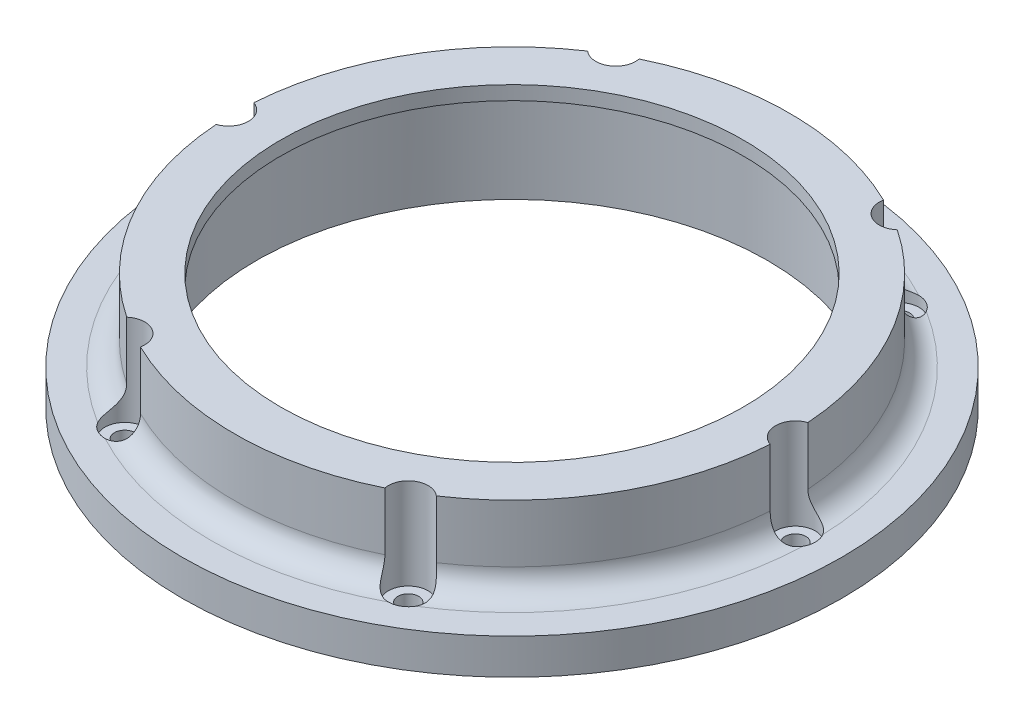
SolidWorks part; units mm, degrees
ref_plane "Front Plane" through (0, 0, 0) normal (0, 0, 1) x (1, 0, 0)
ref_plane "Top Plane" through (0, 0, 0) normal (0, 1, 0) x (1, 0, 0)
ref_plane "Right Plane" through (0, 0, 0) normal (1, 0, 0) x (0, 0, -1)
sketch "Sketch1" plane through (0, 0, 0) normal (0, 1, 0) x (1, 0, 0)
  circle A0 centre (0, 0) radius 61.25 construction
  circle A1 centre (0, 0) radius 55.25
  circle A2 centre (0, 0) radius 60
  dimension "D1" = 122.5
  dimension "D2" = 110.5
  dimension "D3" = 120
extrude "Boss-Extrude1" add sketch "Sketch1" along normal blind 22
sketch "Sketch2" plane through (0, 0, 0) normal (0, -1, 0) x (1, 0, 0)
  circle A0 centre (0, 0) radius 61.25 construction
  circle A1 centre (0, 0) radius 71.25
  circle A2 centre (0, 0) radius 60 construction
  circle A3 centre (0, 0) radius 60
  dimension "D1" = 122.5
  dimension "D2" = 10
extrude "Boss-Extrude2" add sketch "Sketch2" against normal blind 7.5
sketch "Sketch11" plane through (0, 22, 0) normal (0, 1, 0) x (1, 0, 0)
  circle A2 centre (0, 0) radius 60
  circle A3 centre (0, 0) radius 50
  dimension "D1" = 120
  dimension "D2" = 100
extrude "Boss-Extrude5" add sketch "Sketch11" along normal blind 3
hole_wizard "CBORE for M4 SBHCS1" positions "Sketch6" profile "Sketch5" counterbore size "M4" standard "ANSI Metric" end condition through all
sketch "Sketch6" plane through (0, 7.5, 0) normal (0, 1, 0) x (1, 0, 0)
  circle A0 centre (0, 0) radius 61.25 construction
  point P0 (-61.25, 0)
  dimension "D1" = 122.5
sketch "Sketch5" plane through (-61.25, 7.5, 0) normal (1, 0, 0) x (0, 0, 1)
  line L0 (0, 0) -> (0, 7.5)
  line L1 (0, 7.5) -> (2.25, 7.5)
  line L3 (2.25, 7.5) -> (2.25, 2.2)
  line L4 (2.25, 2.2) -> (4.3, 2.2)
  line L5 (4.3, 2.2) -> (4.3, 0)
  line L7 (4.3, 0) -> (0, 0)
  line L11 (0, -6.35) -> (0, 107.95) construction
  dimension "Thru Hole Dia." = 4.5
  dimension "Thru Hole Depth" = 7.5
  dimension "C'Bore Dia." = 8.6
  dimension "C'Bore Depth" = 2.2
fillet "Fillet2" radius 5 1 edges at (60, 7.5, 0)
sketch "Sketch7" plane through (0, 7.5, 0) normal (0, 1, 0) x (1, 0, 0)
  circle A1 centre (-61.25, 0) radius 4.3
  circle A2 centre (-61.25, 0) radius 4.3
  dimension "D1" = 0
extrude "Cut-Extrude1" cut sketch "Sketch7" along normal through all
pattern_circular "CirPattern1" count 6 over 360 about axis through (0, 7.5, 0) along (0, -1, 0) of "Cut-Extrude1", "CBORE for M4 SBHCS1"
sketch "Sketch10" plane through (0, 0, 0) normal (0, -1, 0) x (1, 0, 0)
  circle A0 centre (0, 0) radius 55.25 construction
  circle A1 centre (0, 0) radius 71.25
  circle A2 centre (0, 0) radius 71.25
  circle A3 centre (61.25, 0) radius 2.25 construction
  circle A4 centre (30.625, 53.0441) radius 2.25 construction
  circle A5 centre (-30.625, 53.0441) radius 2.25 construction
  circle A6 centre (-61.25, 0) radius 2.25 construction
  circle A7 centre (-30.625, -53.0441) radius 2.25 construction
  circle A8 centre (30.625, -53.0441) radius 2.25 construction
  circle A9 centre (0, 0) radius 55.25
  circle A10 centre (61.25, 0) radius 2.25
  circle A11 centre (30.625, 53.0441) radius 2.25
  circle A12 centre (-30.625, 53.0441) radius 2.25
  circle A13 centre (-61.25, 0) radius 2.25
  circle A14 centre (-30.625, -53.0441) radius 2.25
  circle A15 centre (30.625, -53.0441) radius 2.25
  dimension "D1" = 0
extrude "Boss-Extrude4" add sketch "Sketch10" along normal blind 0.2
